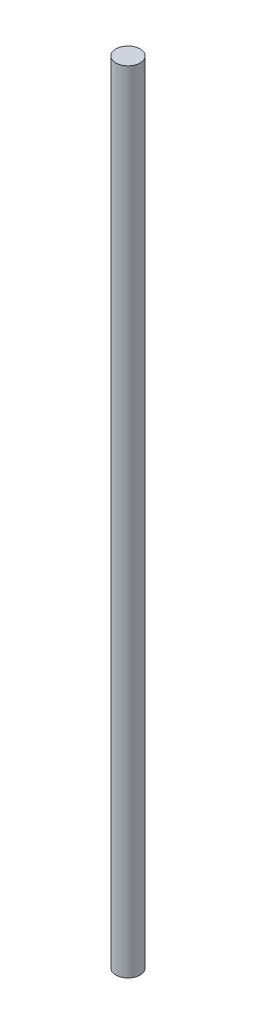
SolidWorks part; units mm, degrees
ref_plane "Front Plane" through (0, 0, 0) normal (0, 0, 1) x (1, 0, 0)
ref_plane "Top Plane" through (0, 0, 0) normal (0, 1, 0) x (1, 0, 0)
ref_plane "Right Plane" through (0, 0, 0) normal (1, 0, 0) x (0, 0, -1)
sketch "Sketch2" plane through (0, 0, 0) normal (0, 1, 0) x (1, 0, 0)
  circle A0 centre (0, 0) radius 2
  dimension "D1" = 4
extrude "Boss-Extrude1" add sketch "Sketch2" along normal blind 130
